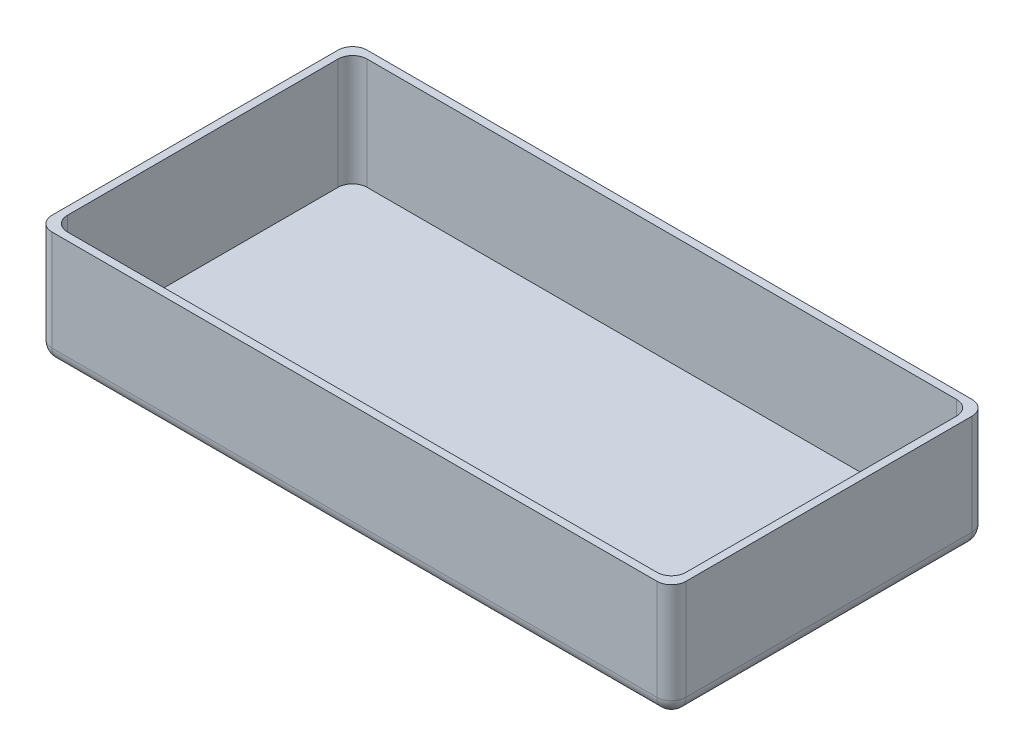
SolidWorks part; units mm, degrees
ref_plane "Спереди" through (0, 0, 0) normal (0, 0, 1) x (1, 0, 0)
ref_plane "Сверху" through (0, 0, 0) normal (0, 1, 0) x (1, 0, 0)
ref_plane "Справа" through (0, 0, 0) normal (1, 0, 0) x (0, 0, -1)
sketch "Sketch1" plane through (0, 0, 0) normal (0, 1, 0) x (1, 0, 0)
  line L0 (-65.6, -32.6) -> (-65.6, 32.6)
  line L1 (-64, -31) -> (64, -31)
  line L2 (-64, -31) -> (-64, 31)
  line L3 (-64, 31) -> (64, 31)
  line L4 (64, -31) -> (64, 31)
  line L5 (-64, -31) -> (64, 31) construction
  line L6 (-64, 31) -> (64, -31) construction
  line L7 (-65.6, 32.6) -> (65.6, 32.6)
  line L8 (65.6, -32.6) -> (65.6, 32.6)
  line L9 (-65.6, -32.6) -> (65.6, -32.6)
  point P0 (0, 0)
  dimension "D1" = 1.6
  dimension "D2" = 62
extrude "Boss-Extrude1" add sketch "Sketch1" along normal blind 23
sketch "Sketch2" plane through (0, 0, 0) normal (0, -1, 0) x (1, 0, 0)
  line L1 (-65.6, -32.6) -> (65.6, -32.6)
  line L2 (-65.6, -32.6) -> (-65.6, 32.6)
  line L3 (-65.6, 32.6) -> (65.6, 32.6)
  line L4 (65.6, -32.6) -> (65.6, 32.6)
  line L5 (-65.6, -32.6) -> (65.6, 32.6) construction
  line L6 (-65.6, 32.6) -> (65.6, -32.6) construction
  point P0 (0, 0)
extrude "Boss-Extrude2" add sketch "Sketch2" along normal blind 0.8
fillet "Fillet1" radius 3 8 edges at (65.6, 11.1, -32.6) (-65.6, 11.1, -32.6) (-65.6, 11.1, 32.6) (-64, 11.5, 31) (65.6, 11.1, 32.6) (64, 11.5, 31) (64, 11.5, -31) (-64, 11.5, -31)
fillet "Fillet2" radius 3 8 edges at (64.7213, -0.8, 31.7213) (65.6, -0.8, 0) (64.7213, -0.8, -31.7213) (0, -0.8, -32.6) (-64.7213, -0.8, -31.7213) (-65.6, -0.8, 0) (-64.7213, -0.8, 31.7213) (0, -0.8, 32.6)
